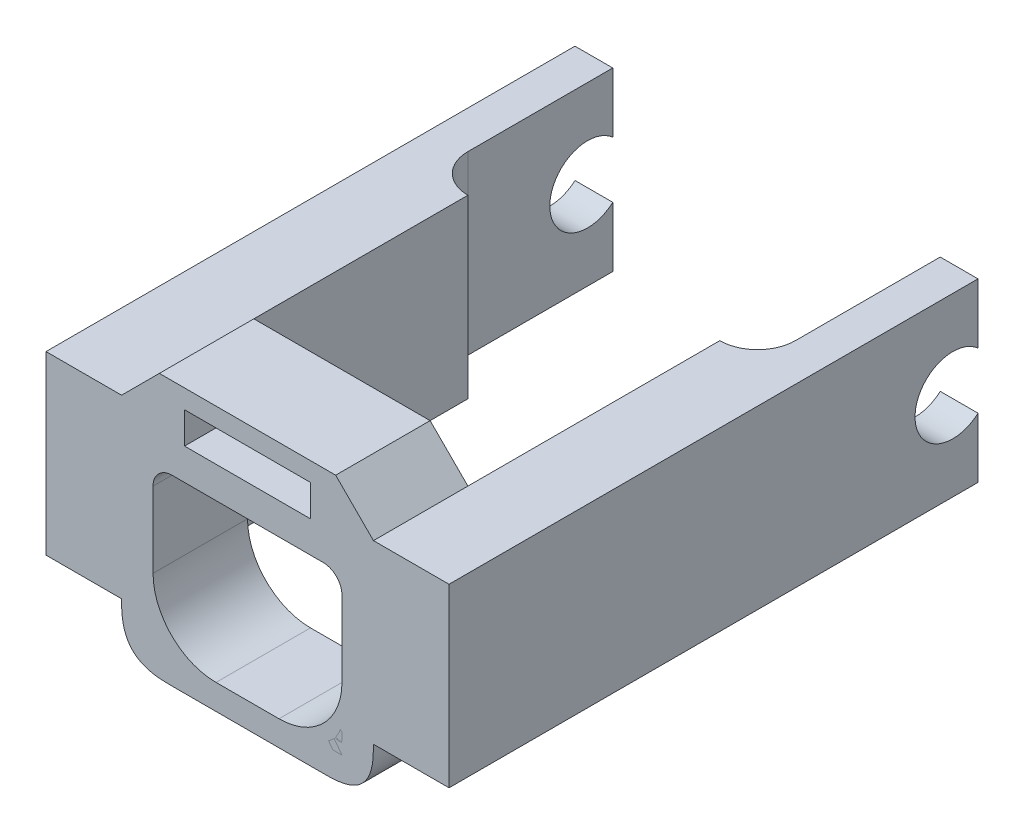
SolidWorks part; units mm, degrees
ref_plane "Front Plane" through (0, 0, 0) normal (0, 0, 1) x (1, 0, 0)
ref_plane "Top Plane" through (0, 0, 0) normal (0, 1, 0) x (1, 0, 0)
ref_plane "Right Plane" through (0, 0, 0) normal (1, 0, 0) x (0, 0, -1)
sketch "Sketch1" plane through (0, 0, 0) normal (0, 0, 1) x (1, 0, 0)
  line L0 (-15, 0) -> (0, 0)
  line L1 (0, 0) -> (0, -12.5)
  line L2 (0, -12.5) -> (-15, -12.5)
  line L3 (-15, -12.5) -> (-15, 0)
  line L4 (-17.5, 6.5) -> (-17.5, -14.5)
  line L5 (-17.5, -14.5) -> (2.5, -14.5)
  line L6 (2.5, -14.5) -> (2.5, 6.5)
  line L7 (-17.5, 6.5) -> (2.5, 6.5)
  dimension "D1" = 15
  dimension "D2" = 12.5
  dimension "D3" = 6.5
  dimension "D4" = 21
  dimension "D5" = 20
  dimension "D6" = 2.5
extrude "Boss-Extrude1" add sketch "Sketch1" along normal blind 7.5
fillet "Fillet1" radius 4 2 edges at (-17.5, -14.5, 3.75) (2.5, -14.5, 3.75) curvature continuous yes
ref_plane "Plane1" through (-15, -12.5, 7.5) normal (0, -1, 0) x (-1, 0, 0)
sketch "Sketch3" plane through (0, 0, 7.5) normal (0, 0, 1) x (1, 0, 0)
  line L1 (0, 0) -> (-10, -12.5)
  line L2 (-16.65, -12.5) -> (-13.35, -12.5) construction
  line L3 (-15, 0) -> (-15, -1.5)
  line L4 (-15, 0) -> (-15, -12.5) construction
  line L5 (-15, 0) -> (-13.5, 0)
  arc A0 (-15, -1.5) -> (-13.5, 0) centre (-13.5, -1.5) cw
  line M13 (-15, -12.5) -> (-15, 0)
  line M14 (-15, 0) -> (0, 0)
extrude "Boss-Extrude2" add sketch "Sketch3" against normal blind 7.5 contours A0 M13 M14 region at (-14.6649, -0.3351, 7.5)
sketch "Sketch4" plane through (0, 0, 7.5) normal (0, 0, 1) x (1, 0, 0)
  line L0 (0, 0) -> (0, -1.4954)
  line L1 (0, -12.5) -> (0, 0) construction
  line L2 (0, 0) -> (-1.4954, 0)
  line L3 (0, 0) -> (-13.5, 0) construction
  arc A0 (0, -1.4954) -> (-1.4954, 0) centre (-1.4954, -1.4954) ccw
extrude "Boss-Extrude3" add sketch "Sketch4" against normal blind 7.5
sketch "Sketch6" plane through (0, 0, 7.5) normal (0, 0, 1) x (1, 0, 0)
  line L0 (0, -12.5) -> (0, -10)
  line L1 (0, -12.5) -> (0, -1.4954) construction
  line L2 (0, -12.5) -> (-2.5, -12.5)
  line L3 (-15, -12.5) -> (0, -12.5) construction
  arc A0 (-2.5, -12.5) -> (0, -10) centre (-2.5, -10) ccw
extrude "Boss-Extrude4" add sketch "Sketch6" against normal blind 7.5 separate body
sketch "Sketch7" plane through (0, 0, 7.5) normal (0, 0, 1) x (1, 0, 0)
  line L0 (-15, -12.5) -> (-10, -12.5)
  line L1 (-16.65, -12.5) -> (-13.35, -12.5) construction
  line L2 (-15, -1.5) -> (-15, -12.5) construction
  line L3 (-15, -12.5) -> (-15, -7.5)
  line L4 (0, -12.5) -> (-5, -12.5)
  line L5 (-15, -12.5) -> (0, -12.5) construction
  line L6 (0, -12.5) -> (0, -7.5)
  line L7 (0, -12.5) -> (0, -1.4954) construction
  arc A0 (-10, -12.5) -> (-15, -7.5) centre (-10, -7.5) cw
  arc A1 (-5, -12.5) -> (0, -7.5) centre (-5, -7.5) ccw
extrude "Boss-Extrude5" add sketch "Sketch7" against normal blind 7.5
chamfer "Chamfer1" distance 3 angle 45 2 edges at (2.5, 6.5, 3.75) (-17.5, 6.5, 3.75)
sketch "Sketch8" plane through (0, 0, 7.5) normal (0, 0, 1) x (1, 0, 0)
  line L0 (-12.5, 5) -> (-2.5, 5)
  line L1 (-2.5, 5) -> (-2.5, 2.5)
  line L2 (-2.5, 2.5) -> (-12.5, 2.5)
  line L3 (-12.5, 2.5) -> (-12.5, 5)
  line L4 (-5.8308, -14.5) -> (-5.8308, -11.5283)
  line L5 (-13.5, -14.5) -> (-1.5, -14.5) construction
  line L6 (-5.8308, -11.5283) -> (-4.4006, -11.5283)
  line L7 (-4.4006, -11.5283) -> (-4.4006, -14.5)
  line L8 (-17.5, 3.5) -> (-17.5, -10.5) construction
  line L10 (-1.4954, 0) -> (-13.5, 0) construction
  dimension "D1" = 5
  dimension "D2" = 2.5
  dimension "D3" = 2.5
extrude "Cut-Extrude1" cut sketch "Sketch8" against normal blind 7.5 contours L3 L2 L1 L0 region at (-7.5, 3.75, 7.5)
sketch "Sketch9" plane through (0, 0, 7.5) normal (0, 0, 1) x (1, 0, 0)
  line L0 (-13.5, -14.5) -> (-1.5, -14.5) construction
  line L1 (-6.1419, -13.5) -> (-4.1419, -13.5)
  line L2 (-6.1419, -13.5) -> (-6.1419, -14.5)
  line L3 (-6.1419, -14.5) -> (-4.1419, -14.5)
  line L4 (-4.1419, -13.5) -> (-4.1419, -14.5)
  dimension "D1" = 1
sketch "Sketch12" plane through (0, 0, 0) normal (0, 0, -1) x (-1, 0, 0)
  line L10 (14.5, 6.5) -> (0.5, 6.5)
  line L11 (0.5, 6.5) -> (-2.5, 3.5)
  line L12 (-2.5, 3.5) -> (-2.5, -10.5)
  line L13 (1.5, -14.5) -> (13.5, -14.5)
  line L14 (17.5, -10.5) -> (17.5, 3.5)
  line L15 (17.5, 3.5) -> (14.5, 6.5)
  line L18 (-2.5, 3.5) -> (-2.5, -10.5)
  spline S2 degree 2 poles (67.845, 987.0209) (-3.6492, 6.7622) (-2.4812, -11.3302) (-2.4524, -11.7775) (-2.3691, -12.1519) (-2.1636, -13.0767) (-1.6244, -13.6183) (-1.0848, -14.1602) (-0.1577, -14.3678) (0.2161, -14.4515) (0.6646, -14.4809) (18.738, -15.6634) (998.9799, 56.3297) knots -7.651516 -7.651516 -7.651516 0.125 0.125 0.25 0.25 0.5 0.5 0.75 0.75 0.875 0.875 8.610168 8.610168 8.610168 only from (-2.5, -10.5) to (1.5, -14.5)
  spline S3 degree 2 poles (-984.0209, 55.845) (-3.7622, -15.6492) (14.3302, -14.4812) (14.7775, -14.4524) (15.1519, -14.3691) (16.0767, -14.1636) (16.6183, -13.6244) (17.1602, -13.0848) (17.3678, -12.1577) (17.4515, -11.7839) (17.4809, -11.3354) (18.6634, 6.738) (-53.3297, 986.9799) knots -7.651516 -7.651516 -7.651516 0.125 0.125 0.25 0.25 0.5 0.5 0.75 0.75 0.875 0.875 8.610168 8.610168 8.610168 only from (13.5, -14.5) to (17.5, -10.5)
  dimension "D1" = 0
sketch "Sketch19" plane through (0, 0, 0) normal (0, 0, -1) x (-1, 0, 0)
  line L0 (17.5, 3.5) -> (23.5, 3.5)
  line L1 (23.5, 3.5) -> (23.5, -10.5)
  line L2 (23.5, -10.5) -> (17.5, -10.5)
  line L3 (17.5, -10.5) -> (17.5, 3.5)
  line L4 (7.4977, 0) -> (7.5, -12.5)
  line L5 (1.4954, 0) -> (13.5, 0) construction
  line L6 (10, -12.5) -> (5, -12.5) construction
  line M16 (17.5, -10.5) -> (17.5, 3.5)
extrude "Boss-Extrude10" add sketch "Sketch19" along normal blind 45 and the other way blind 7.5 contours L2 L1 L0 M16 region at (-20.5, -3.5, 0)
ref_plane "Plane3" through (-7.5, 0, 0) normal (-1, 0, 0) x (0, 0, 1)
ref_plane "Plane4" through (0, 3.5, 0) normal (0, 1, 0) x (1, 0, 0)
sketch "Sketch24" plane through (0, 3.5, 0) normal (0, 1, 0) x (1, 0, 0)
  line L0 (-20.5, 45) -> (-20.5, 20)
  line L1 (-17.5, 45) -> (-23.5, 45) construction
  line L2 (-20.5, 20) -> (-17.5, 20)
  line L3 (-17.5, 0) -> (-17.5, 45) construction
extrude "Cut-Extrude5" cut sketch "Sketch24" against normal blind 15 and the other way through all
fillet "Fillet2" radius 3 1 edges at (-20.5, -3.5, -20)
mirror "Mirror4" about plane through (-7.5, 0, 0) normal (-1, 0, 0) of "Boss-Extrude10"
sketch "Sketch31" plane through (0, 3.5, 0) normal (0, 1, 0) x (1, 0, 0)
  line L0 (5.5, 45) -> (5.5, 20)
  line L1 (2.5, 45) -> (8.5, 45) construction
  line L2 (5.5, 20) -> (2.5, 20)
  line L3 (2.5, 0) -> (2.5, 45) construction
sketch "Sketch32" plane through (2.5, 0, 0) normal (-1, 0, 0) x (0, 0, 1)
  line L0 (-20, 3.5) -> (-20, -10.5)
  line L1 (0, -10.5) -> (-45, -10.5) construction
  line L2 (-20, -10.5) -> (-44.5249, -10.5)
  line L3 (-45, 3.5) -> (-45, -10.5)
  line L4 (-45, 3.5) -> (-20.3087, 3.5)
  line L5 (0, 3.5) -> (-45, 3.5) construction
  line L6 (-45, -10.5) -> (-44.5249, -10.5)
  line L7 (-20.3087, 3.5) -> (-20, 3.5)
extrude "Cut-Extrude16" cut sketch "Sketch32" against normal blind 3
fillet "Fillet3" radius 3 1 edges at (5.5, -3.5, -20)
sketch "Sketch33" plane through (8.5, 0, 0) normal (1, 0, 0) x (0, 0, -1)
  line L2 (45, 3.5) -> (34.5, 3.5)
  line L3 (45, 3.5) -> (20, 3.5) construction
  line L4 (3.4836, 3.5) -> (-3.4836, 3.5) construction
  line L5 (34.5, 3.5) -> (34.5, -10.5)
  line L6 (-7.5, -10.5) -> (45, -10.5) construction
  line L7 (34.5, -10.5) -> (45, -10.5)
  line L8 (45, -10.5) -> (45, 3.5)
  circle A0 centre (32.5, -3.5) radius 3
  line M1 (-7.5, -10.5) -> (45, -10.5)
  line M2 (45, -10.5) -> (45, 3.5)
  line M3 (45, 3.5) -> (-7.5, 3.5)
extrude "Cut-Extrude17" cut sketch "Sketch33" against normal blind 35 contours L5 A0 | L5 A0 | A0 L5 M1 M2 M3 region at (8.5, -3.5, -39.8543) region at (8.5, -3.5, -34.9063) region at (8.5, -3.5, -32.204)
sketch "Sketch34" plane through (8.5, 0, 0) normal (1, 0, 0) x (0, 0, -1)
